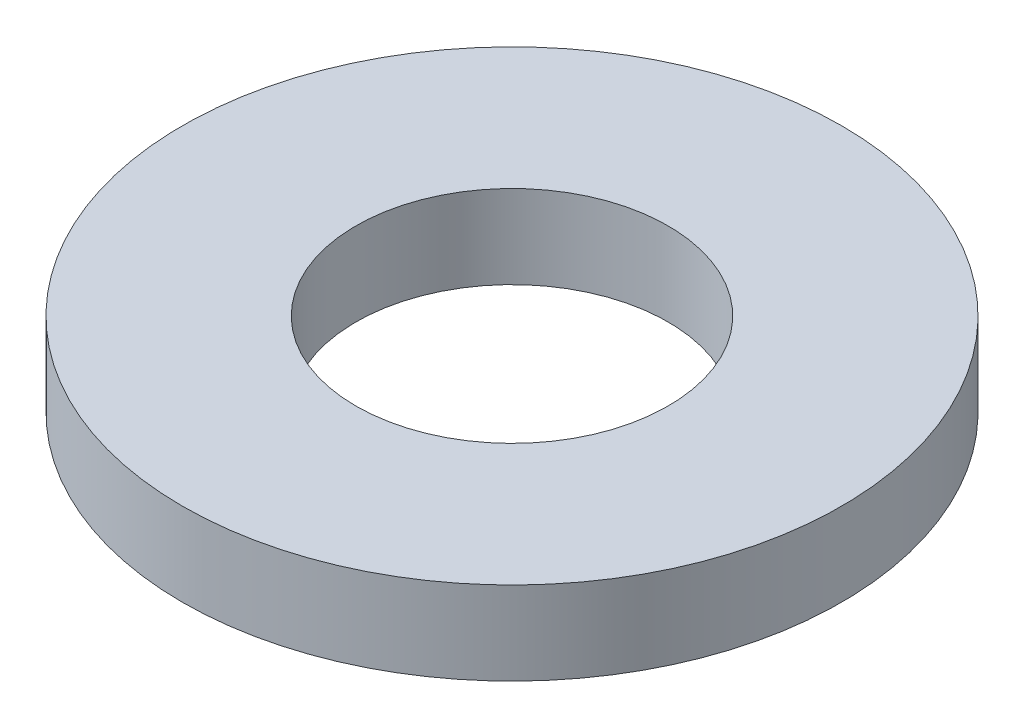
SolidWorks part; units mm, degrees
ref_plane "Front Plane" through (0, 0, 0) normal (0, 0, 1) x (1, 0, 0)
ref_plane "Top Plane" through (0, 0, 0) normal (0, 1, 0) x (1, 0, 0)
ref_plane "Right Plane" through (0, 0, 0) normal (1, 0, 0) x (0, 0, -1)
sketch "Sketch1" plane through (0, 0, 0) normal (0, 1, 0) x (1, 0, 0)
  circle A0 centre (0, 0) radius 95
  dimension "FLANGE_OD" = 190
extrude "Boss-Extrude1" add sketch "Sketch1" along normal blind 24
sketch "Sketch2" plane through (0, 0, 0) normal (0, 1, 0) x (1, 0, 0)
  circle A0 centre (0, 0) radius 45
  dimension "BORE_D" = 90
extrude "Cut-Extrude1" cut sketch "Sketch2" along normal through all
sketch "Sketch3" plane through (0, 24, 0) normal (0, 1, 0) x (1, 0, 0)
  circle A0 centre (0, 0) radius 30.1539 construction
  circle A1 centre (-30.1539, 0) radius 8.7755
  dimension "BOLT_D" = 17.551
  dimension "BOLT_PCD" = 60.3078
extrude "Cut-Extrude2" cut sketch "Sketch3" against normal blind 19.1716 rebuild error yes
pattern_circular "CirPattern1" count 5 over 360 rebuild error yes
